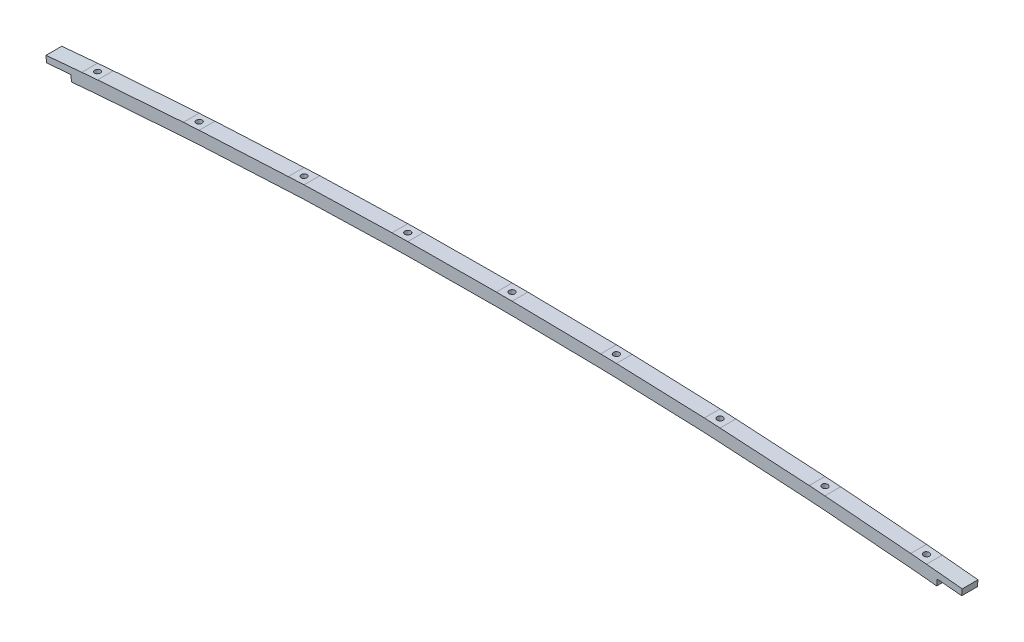
SolidWorks part; units mm, degrees
ref_plane "Front Plane" through (0, 0, 0) normal (0, 0, 1) x (1, 0, 0)
ref_plane "Top Plane" through (0, 0, 0) normal (0, 1, 0) x (1, 0, 0)
ref_plane "Right Plane" through (0, 0, 0) normal (1, 0, 0) x (0, 0, -1)
sketch "Sketch1" plane through (0, 0, 4.0971) normal (0, 0, -1) x (-1, 0, 0)
  line L0 (266.8785, -57.7348) -> (266.5476, -61.5108) construction
  line L1 (281.6204, -58.9778) -> (281.9405, -55.1813) construction
  line L2 (266.8785, -57.7348) -> (281.6204, -58.9778) construction
  line L3 (266.8785, -57.7348) -> (266.5476, -61.5108)
  line L4 (281.6204, -58.9778) -> (281.9405, -55.1813)
  line L5 (266.8785, -57.7348) -> (281.6204, -58.9778)
  line L6 (-271.5116, -61.3706) -> (-271.8645, -57.577) construction
  line L7 (-256.781, -60.0001) -> (-271.5116, -61.3706) construction
  line L8 (-256.781, -60.0001) -> (-256.4175, -63.7732) construction
  line L9 (-271.5116, -61.3706) -> (-271.8645, -57.577)
  line L10 (250.8, -52.4747) -> (250.1692, -60.0685)
  line L11 (250.1692, -60.0685) -> (259.6615, -60.857)
  line L12 (259.6615, -60.857) -> (260.2923, -53.2631)
  line L13 (260.2923, -53.2631) -> (250.8, -52.4747)
  line L14 (250.8, -52.4747) -> (250.1692, -60.0685)
  line L15 (250.1692, -60.0685) -> (259.6615, -60.857)
  line L16 (259.6615, -60.857) -> (260.2923, -53.2631)
  line L17 (260.2923, -53.2631) -> (250.8, -52.4747)
  line L18 (189.37, -48.1316) -> (188.9015, -55.7372)
  line L19 (188.9015, -55.7372) -> (198.4085, -56.3228)
  line L20 (198.4085, -56.3228) -> (198.877, -48.7172)
  line L21 (198.877, -48.7172) -> (189.37, -48.1316)
  line L22 (189.37, -48.1316) -> (188.9015, -55.7372)
  line L23 (188.9015, -55.7372) -> (198.4085, -56.3228)
  line L24 (198.4085, -56.3228) -> (198.877, -48.7172)
  line L25 (198.877, -48.7172) -> (189.37, -48.1316)
  line L26 (126.3109, -45.0468) -> (126.0095, -52.6608)
  line L27 (126.0095, -52.6608) -> (135.5271, -53.0375)
  line L28 (135.5271, -53.0375) -> (135.8284, -45.4235)
  line L29 (135.8284, -45.4235) -> (126.3109, -45.0468)
  line L30 (126.3109, -45.0468) -> (126.0095, -52.6608)
  line L31 (126.0095, -52.6608) -> (135.5271, -53.0375)
  line L32 (135.5271, -53.0375) -> (135.8284, -45.4235)
  line L33 (135.8284, -45.4235) -> (126.3109, -45.0468)
  line L34 (63.26, -43.3484) -> (63.1258, -50.9673)
  line L35 (63.1258, -50.9673) -> (72.6493, -51.135)
  line L36 (72.6493, -51.135) -> (72.7836, -43.5162)
  line L37 (72.7836, -43.5162) -> (63.26, -43.3484)
  line L38 (63.26, -43.3484) -> (63.1258, -50.9673)
  line L39 (63.1258, -50.9673) -> (72.6493, -51.135)
  line L40 (72.6493, -51.135) -> (72.7836, -43.5162)
  line L41 (72.7836, -43.5162) -> (63.26, -43.3484)
  line L42 (0.2177, -43.034) -> (0.2507, -50.6539)
  line L43 (0.2507, -50.6539) -> (9.7756, -50.6127)
  line L44 (9.7756, -50.6127) -> (9.7426, -42.9928)
  line L45 (9.7426, -42.9928) -> (0.2177, -43.034)
  line L46 (0.2177, -43.034) -> (0.2507, -50.6539)
  line L47 (0.2507, -50.6539) -> (9.7756, -50.6127)
  line L48 (9.7756, -50.6127) -> (9.7426, -42.9928)
  line L49 (9.7426, -42.9928) -> (0.2177, -43.034)
  line L50 (-53.2947, -43.8527) -> (-62.8164, -44.1028)
  line L51 (-62.8164, -44.1028) -> (-62.6162, -51.7202)
  line L52 (-62.6162, -51.7202) -> (-53.0945, -51.47)
  line L53 (-53.0945, -51.47) -> (-53.2947, -43.8527)
  line L54 (-53.2947, -43.8527) -> (-62.8164, -44.1028)
  line L55 (-62.8164, -44.1028) -> (-62.6162, -51.7202)
  line L56 (-62.6162, -51.7202) -> (-53.0945, -51.47)
  line L57 (-53.0945, -51.47) -> (-53.2947, -43.8527)
  line L58 (-125.4926, -46.5783) -> (-125.0596, -54.186)
  line L59 (-125.0596, -54.186) -> (-115.55, -53.6447)
  line L60 (-115.55, -53.6447) -> (-115.983, -46.037)
  line L61 (-115.983, -46.037) -> (-125.4926, -46.5783)
  line L62 (-125.4926, -46.5783) -> (-125.0596, -54.186)
  line L63 (-125.0596, -54.186) -> (-115.55, -53.6447)
  line L64 (-115.55, -53.6447) -> (-115.983, -46.037)
  line L65 (-115.983, -46.037) -> (-125.4926, -46.5783)
  line L66 (-179.3585, -49.7267) -> (-188.8601, -50.3945)
  line L67 (-188.8601, -50.3945) -> (-188.3258, -57.9958)
  line L68 (-188.3258, -57.9958) -> (-178.8243, -57.3279)
  line L69 (-178.8243, -57.3279) -> (-179.3585, -49.7267)
  line L70 (-179.3585, -49.7267) -> (-188.8601, -50.3945)
  line L71 (-188.8601, -50.3945) -> (-188.3258, -57.9958)
  line L72 (-188.3258, -57.9958) -> (-178.8243, -57.3279)
  line L73 (-178.8243, -57.3279) -> (-179.3585, -49.7267)
  line L74 (-240.7486, -54.6011) -> (-250.2337, -55.4716)
  line L75 (-250.2337, -55.4716) -> (-249.5373, -63.0597)
  line L76 (-249.5373, -63.0597) -> (-240.0522, -62.1892)
  line L77 (-240.0522, -62.1892) -> (-240.7486, -54.6011)
  line L78 (-240.7486, -54.6011) -> (-250.2337, -55.4716)
  line L79 (-250.2337, -55.4716) -> (-249.5373, -63.0597)
  line L80 (-249.5373, -63.0597) -> (-240.0522, -62.1892)
  line L81 (-240.0522, -62.1892) -> (-240.7486, -54.6011)
  line L82 (-256.781, -60.0001) -> (-271.5116, -61.3706)
  line L83 (-256.781, -60.0001) -> (-256.4175, -63.7732)
  line L84 (-256.4175, -63.7732) -> (-249.5373, -63.0597)
  line L85 (-240.0522, -62.1892) -> (-188.3258, -57.9958)
  line L86 (-178.8243, -57.3279) -> (-125.0596, -54.186)
  line L87 (-115.55, -53.6447) -> (-62.6162, -51.7202)
  line L88 (-53.0945, -51.47) -> (0.2507, -50.6539)
  line L89 (9.7756, -50.6127) -> (63.1258, -50.9673)
  line L90 (72.6493, -51.135) -> (126.0095, -52.6608)
  line L91 (135.5271, -53.0375) -> (188.9015, -55.7372)
  line L92 (198.4085, -56.3228) -> (250.1692, -60.0685)
  line L93 (259.6615, -60.857) -> (266.5476, -61.5108)
  line L94 (260.2923, -53.2631) -> (281.9405, -55.1813)
  line L95 (250.8, -52.4747) -> (198.877, -48.7172)
  line L96 (189.37, -48.1316) -> (135.8284, -45.4235)
  line L97 (126.3109, -45.0468) -> (72.7836, -43.5162)
  line L98 (63.26, -43.3484) -> (9.7426, -42.9928)
  line L99 (0.2177, -43.034) -> (-53.2947, -43.8527)
  line L100 (-62.8164, -44.1028) -> (-115.983, -46.037)
  line L101 (-125.4926, -46.5783) -> (-179.3585, -49.7267)
  line L102 (-188.8601, -50.3945) -> (-240.7486, -54.6011)
  line L103 (-250.2337, -55.4716) -> (-271.8645, -57.577)
  line L104 (5.0131, -50.6333) -> (4.9802, -43.0134) construction
  line L117 (135.8284, -45.4235) -> (126.3109, -45.0468)
  line L118 (135.5271, -53.0375) -> (135.8284, -45.4235)
  line L119 (126.0095, -52.6608) -> (135.5271, -53.0375)
  line L120 (126.3109, -45.0468) -> (126.0095, -52.6608)
  line L121 (135.8284, -45.4235) -> (126.3109, -45.0468)
  line L122 (135.5271, -53.0375) -> (135.8284, -45.4235)
  line L123 (126.0095, -52.6608) -> (135.5271, -53.0375)
  line L124 (126.3109, -45.0468) -> (126.0095, -52.6608)
  arc A0 (281.9405, -55.1813) -> (288.7978, -49.4309) centre (282.474, -48.8537) ccw construction
  arc A1 (281.9405, -55.1813) -> (288.7978, -49.4309) centre (282.474, -48.8537) ccw
  arc A2 (-278.7713, -51.8861) -> (-271.8645, -57.577) centre (-272.4528, -51.2543) ccw construction
  arc A3 (-278.7713, -51.8861) -> (-271.8645, -57.577) centre (-272.4528, -51.2543) ccw
  spline S0 degree 3 poles (1381.3553, 110.3869) (955.6577, -11.7424) (284.2428, -157.6412) (-383.9269, 71.7343) (-656.3129, 323.6229) knots -1.386382 -1.386382 -1.386382 -1.386382 0.401473 2.862329 2.862329 2.862329 2.862329 only from (397.428, -68.1814) to (266.5476, -61.5108) construction
  spline S1 degree 3 poles (397.428, -68.1814) (395.3421, -68.1512) (351.6556, -67.4439) (307.9828, -65.1415) (266.5476, -61.5108) knots 0.388247 0.388247 0.388247 0.388247 0.401473 0.665255 0.665255 0.665255 0.665255
  spline S2 degree 3 poles (-1372.6706, 98.4731) (-945.9324, -19.9686) (-273.2803, -160.053) (392.8798, 75.0947) (663.0764, 329.3306) knots -1.386382 -1.386382 -1.386382 -1.386382 0.401473 2.862329 2.862329 2.862329 2.862329 only from (-387.2353, -71.5758) to (-256.4175, -63.7732) construction
  spline S3 degree 3 poles (-387.2353, -71.5758) (-385.1497, -71.5276) (-341.4709, -70.4424) (-297.8197, -67.7621) (-256.4175, -63.7732) knots 0.388247 0.388247 0.388247 0.388247 0.401473 0.665255 0.665255 0.665255 0.665255
  dimension "D1" = 0
  dimension "D2" = 0
  dimension "D3" = 0
  dimension "D4" = 0
  dimension "D5" = 0
  dimension "D6" = 0
  dimension "D7" = 0
  dimension "D8" = 0
  dimension "D9" = 0
  dimension "D10" = 0
extrude "Boss-Extrude1" add sketch "Sketch1" along normal blind 4.7625 and the other way blind 4.7625 contours L80 L81 L78 L79 | L79 L103 L9 L82 L83 L84 | L71 L102 L81 L85 | L72 L73 L70 L71 | L62 L101 L73 L86 | L64 L65 L62 L63 | L55 L100 L64 L87 | L56 L57 L54 L55 | L46 L99 L57 L88 | L47 L104 L49 L46 region at (-2.6154, -46.8336, 4.0971) region at (26.4802, -47.2506, 4.0971) region at (57.9554, -47.7864, 4.0971) region at (89.2408, -48.8734, 4.0971) region at (120.5213, -50.1115, 4.0971) region at (152.1835, -51.9535, 4.0971) region at (183.8422, -53.8612, 4.0971) region at (214.4968, -56.2932, 4.0971) region at (245.143, -58.8304, 4.0971) region at (259.0138, -59.176, 4.0971)
sketch "Sketch2" plane through (-3.6548, -39.8223, 0) normal (-0.0914, -0.9958, 0) x (0.9958, -0.0914, 0)
  circle A0 centre (249.4937, 4.0971) radius 3.048
extrude "Cut-Extrude1" cut sketch "Sketch2" against normal blind 3.556
sketch "Sketch3" plane through (-3.3298, -36.2811, 0) normal (-0.0914, -0.9958, 0) x (0.9958, -0.0914, 0)
  circle A0 centre (249.4937, 4.0971) radius 1.778
extrude "Cut-Extrude2" cut sketch "Sketch3" against normal through all
sketch "Sketch4" plane through (-3.1305, -44.5391, 0) normal (-0.0701, -0.9975, 0) x (0.9975, -0.0701, 0)
  circle A0 centre (187.1661, 4.0971) radius 3.048
extrude "Cut-Extrude3" cut sketch "Sketch4" against normal blind 3.556
sketch "Sketch5" plane through (-2.6705, -46.9154, 0) normal (-0.0568, -0.9984, 0) x (-0.9984, 0.0568, 0)
  circle A0 centre (-123.1743, -4.0971) radius 3.048
extrude "Cut-Extrude4" cut sketch "Sketch5" against normal blind 3.556
sketch "Sketch6" plane through (-1.3147, -50.0405, 0) normal (-0.0263, -0.9997, 0) x (0.9997, -0.0263, 0)
  circle A0 centre (59.1905, 4.0971) radius 3.048
extrude "Cut-Extrude5" cut sketch "Sketch6" against normal blind 3.556
sketch "Sketch7" plane through (-0.2191, -50.654, 0) normal (-0.0043, -1, 0) x (-1, 0.0043, 0)
  line L0 (4.794, -8.8596) -> (4.794, 0.6654) construction
  circle A0 centre (4.794, -4.0971) radius 3.048
extrude "Cut-Extrude6" cut sketch "Sketch7" against normal blind 3.556
sketch "Sketch8" plane through (-0.2037, -47.0981, 0) normal (-0.0043, -1, 0) x (1, -0.0043, 0)
  line L0 (-4.794, 1.0491) -> (-4.794, 7.1451) construction
  circle A0 centre (-4.794, 4.0971) radius 1.778
extrude "Cut-Extrude7" cut sketch "Sketch8" against normal through all
sketch "Sketch9" plane through (-1.2213, -46.4858, 0) normal (-0.0263, -0.9997, 0) x (0.9997, -0.0263, 0)
  circle A0 centre (59.1905, 4.0971) radius 1.778
extrude "Cut-Extrude8" cut sketch "Sketch9" against normal through all
sketch "Sketch10" plane through (-2.4684, -43.3652, 0) normal (-0.0568, -0.9984, 0) x (0.9984, -0.0568, 0)
  circle A0 centre (123.1743, 4.0971) radius 1.778
extrude "Cut-Extrude9" cut sketch "Sketch10" against normal through all
sketch "Sketch11" plane through (-2.8811, -40.9919, 0) normal (-0.0701, -0.9975, 0) x (-0.9975, 0.0701, 0)
  circle A0 centre (-187.1661, -4.0971) radius 1.778
extrude "Cut-Extrude10" cut sketch "Sketch11" against normal through all
mirror "Mirror1" about plane through (-4.794, 0.0207, 8.8596) normal (-1, 0.0043, 0) of "Cut-Extrude10", "Cut-Extrude9", "Cut-Extrude8", "Cut-Extrude7", "Cut-Extrude6", "Cut-Extrude5", "Cut-Extrude4", "Cut-Extrude3", "Cut-Extrude2", "Cut-Extrude1", "Boss-Extrude1"
